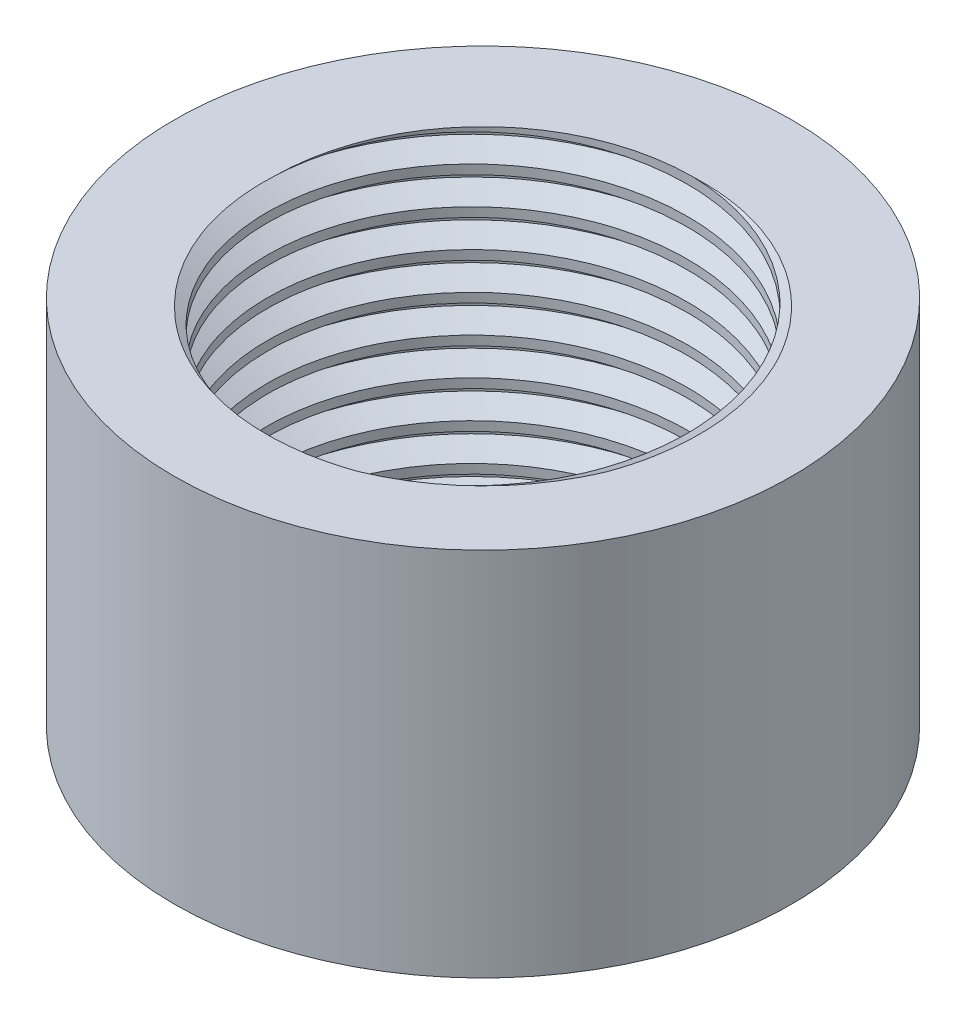
SolidWorks part; units mm, degrees
ref_plane "Front Plane" through (0, 0, 0) normal (0, 0, 1) x (1, 0, 0)
ref_plane "Top Plane" through (0, 0, 0) normal (0, 1, 0) x (1, 0, 0)
ref_plane "Right Plane" through (0, 0, 0) normal (1, 0, 0) x (0, 0, -1)
sketch "Sketch1" plane through (0, 0, 0) normal (0, 1, 0) x (1, 0, 0)
  circle A0 centre (0, 0) radius 12.5
  circle A1 centre (0, 0) radius 8.5
  dimension "D1" = 17
  dimension "D2" = 25
extrude "Boss-Extrude1" add sketch "Sketch1" along normal blind 15
thread "Thread1" pitch 1.5 method cut trim with start face yes trim with end face yes profile "Thread Profile1" start angle 0, offset 1.5, length 0, pitch 1.5, diameter 17
ref_plane "Plane1" through (-8.5, 16.5, 0) normal (0, 0, 1) x (-1, 0, 0)
sketch "Thread Profile1" plane through (-8.5, 16.5, 0) normal (0, 0, 1) x (-1, 0, 0)
  line L0 (0, 0) -> (0, 1.5) construction
  line L1 (0, 0) -> (0.8119, 0.4687)
  line L2 (0.8119, 0.4687) -> (0.8119, 0.6562)
  line L3 (0.8119, 0.6562) -> (0, 1.125)
  line L4 (0.8119, 0.5625) -> (0, 0.5625) construction
  line L11 (0, 0) -> (0, 1.125)
  point P2 (0, 0)
  dimension "Pitch" = 1.5
  dimension "Profile_Angle" = 60
  dimension "Profile_Land" = 0.1875
  dimension "Profile_Height" = 0.8119
